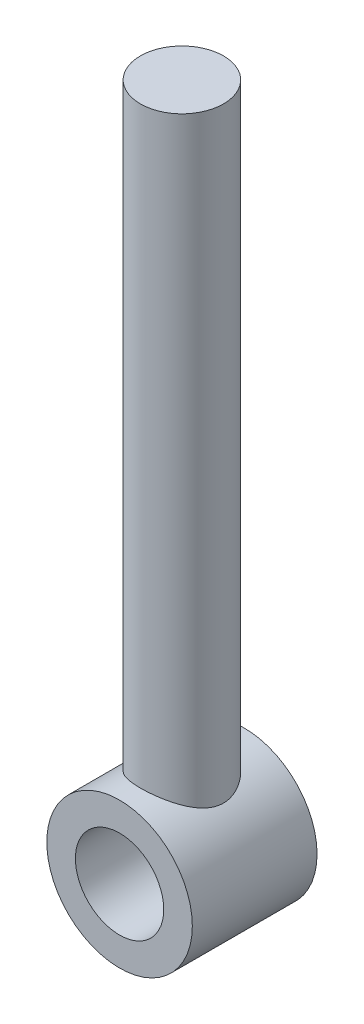
SolidWorks part; units mm, degrees
ref_plane "Front Plane" through (0, 0, 0) normal (0, 0, 1) x (1, 0, 0)
ref_plane "Top Plane" through (0, 0, 0) normal (0, 1, 0) x (1, 0, 0)
ref_plane "Right Plane" through (0, 0, 0) normal (1, 0, 0) x (0, 0, -1)
sketch "Sketch1" plane through (0, 0, 0) normal (0, 0, 1) x (1, 0, 0)
  circle A0 centre (0, 0) radius 11.1125
  dimension "D1" = 22.225
extrude "Boss-Extrude1" add sketch "Sketch1" along normal blind 9.525 and the other way blind 9.525
sketch "Sketch2" plane through (0, 0, 0) normal (0, 1, 0) x (1, 0, 0)
  circle A0 centre (0, 0) radius 6.35
  dimension "D1" = 12.7
extrude "Boss-Extrude2" add sketch "Sketch2" along normal blind 101.6
hole_wizard "1/2 Clearance Hole1" positions "Sketch3" profile "Sketch4" hole size "1/2" standard "ANSI Inch"
sketch "Sketch3" plane through (0, 0, 9.525) normal (0, 0, 1) x (1, 0, 0)
  point P0 (0, 0)
sketch "Sketch4" plane through (0, 0, 9.525) normal (1, 0, 0) x (0, -1, 0)
  line L0 (0, 0) -> (0, 67.5535)
  line L1 (0, 67.5535) -> (6.7462, 63.5)
  line L2 (6.7462, 63.5) -> (6.7462, 0)
  line L5 (6.7462, 0) -> (0, 0)
  line L10 (0, 67.5535) -> (-6.7462, 63.5) construction
  line L11 (0, -6.35) -> (0, 107.95) construction
  dimension "Hole Dia." = 13.4925
  dimension "Hole Depth" = 63.5
  dimension "Drill Angle" = 118
